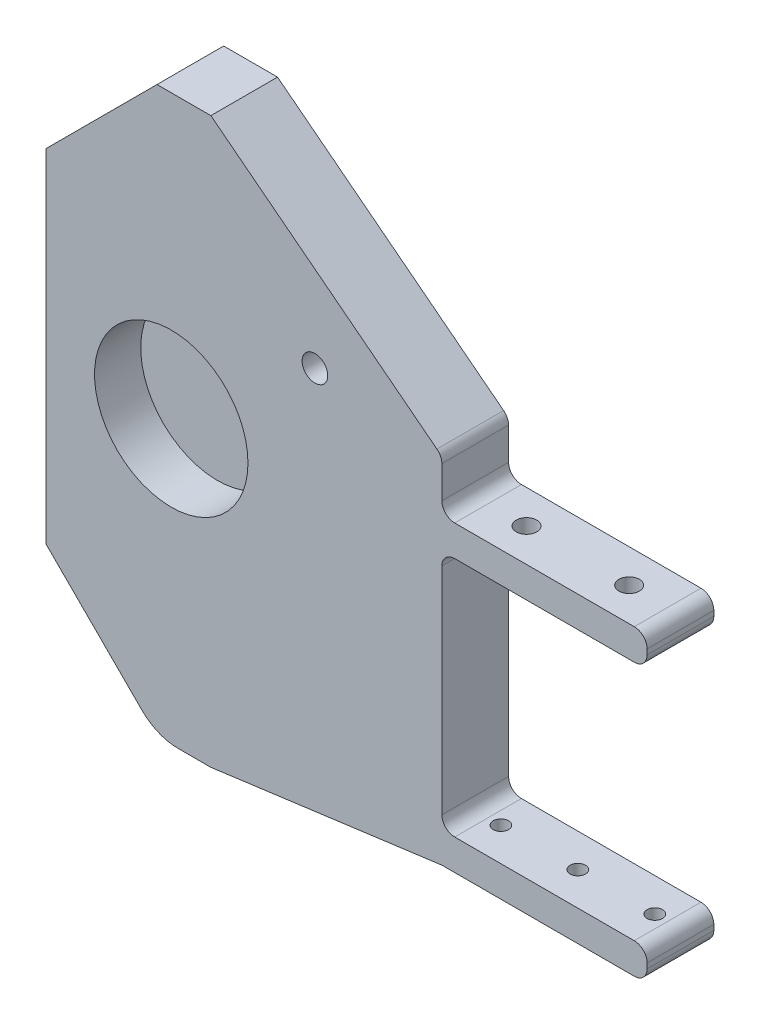
SolidWorks part; units mm, degrees
material "5052-H36"
ref_plane "Plano frontal" through (0, 0, 0) normal (0, 0, 1) x (1, 0, 0)
ref_plane "Plano superior" through (0, 0, 0) normal (0, 1, 0) x (1, 0, 0)
ref_plane "Plano direito" through (0, 0, 0) normal (1, 0, 0) x (0, 0, -1)
sketch "Esboço1" plane through (0, 0, 0) normal (0, 0, 1) x (1, 0, 0)
  line L0 (79.1281, 0) -> (0, 0) construction
  line L3 (4.9801, 55) -> (32.742, 55)
  line L6 (32.742, 55) -> (-22.7817, 55)
  line L12 (-22.7817, 55) -> (-44.3754, 33.4063)
  line L14 (-44.3754, -33.4063) -> (-22.7817, -55)
  line L15 (-22.7817, -55) -> (32.742, -55)
  line L18 (393.8557, 316.0739) -> (396.402, 318.6203) [skipped]
  line L19 (55, 501.996) -> (55, 520.8093) [skipped]
  line L20 (-316.0739, 393.8557) -> (-318.6203, 396.402) [skipped]
  line L21 (32.742, 55) -> (32.742, 10)
  line L22 (32.742, -49) -> (32.742, -55)
  line L23 (32.742, -49) -> (72.742, -49)
  line L25 (32.742, -43) -> (72.742, -43)
  line L26 (72.742, -49) -> (72.742, -43)
  line L27 (32.742, 4) -> (32.742, -43)
  line L28 (32.742, 4) -> (72.742, 4)
  line L30 (32.742, 10) -> (72.742, 10)
  line L31 (72.742, 4) -> (72.742, 10)
  line L32 (-44.3754, 33.4063) -> (-44.3754, -33.4063)
  line L34 (-55, 7.7563) -> (-55, -6.3461) [skipped]
  circle A0 centre (0, 0) radius 15 construction
  arc A3 (4.9801, 55) -> (0, -55.225) centre (0, 0) ccw construction
  point P14 (4.9801, 55)
  dimension "D1" = 30
  dimension "D5" = 110
  dimension "D6" = 40
  dimension "D7" = 6
  dimension "D8" = 6
  dimension "D9" = 45
extrude "Ressalto-extrusão1" add sketch "Esboço1" along normal mid plane 13 contours L14 L15 L3 L6 L12 A0 region at (-0.7875, -1.1016, 0)
sketch "Esboço2" plane through (0, 0, 6.5) normal (0, 0, 1) x (1, 0, 0)
  circle A1 centre (-20, 0) radius 14.95
  dimension "D1" = 29.9
  dimension "D2" = 20
extrude "Corte-extrusão1" cut sketch "Esboço2" against normal blind 9
sketch "Esboço3" plane through (0, 0, 6.5) normal (0, 0, 1) x (1, 0, 0)
  line L0 (-22.7817, -55) -> (32.742, -55) construction
  line L1 (-12.2817, -55) -> (32.742, -49)
  line L2 (32.742, -49) -> (32.742, -55)
  line L3 (32.742, -55) -> (-12.2817, -55)
  line L4 (-12.2817, -55) -> (-12.2817, 66.3095) construction
  line L6 (32.742, 10) -> (72.742, 10) construction
  line L11 (32.742, 55) -> (-12.2817, 55)
  line L12 (-12.2817, 55) -> (32.742, 20)
  line L13 (32.742, 20) -> (32.742, 55)
  circle A0 centre (8, 22.5) radius 2.5
  point P0 (-12.2817, -55)
  dimension "D2" = 5
  dimension "D1" = 10.5
  dimension "D3" = 22.5
  dimension "D4" = 28
  dimension "D5" = 10
extrude "Corte-extrusão2" cut sketch "Esboço3" against normal blind 13
fillet "Filete1" radius 10 1 edges at (-22.7817, -55, 0)
sketch "Esboço4" plane through (0, 0, -6.5) normal (0, 0, -1) x (-1, 0, 0)
  line L0 (44.3754, 33.4063) -> (44.3754, -33.4063) construction
  circle A0 centre (36.3754, 8.4063) radius 2
  circle A1 centre (12.9554, -16.5937) radius 2
  circle A2 centre (22.3754, -27.5937) radius 2
  dimension "D1" = 4
  dimension "D2" = 25
  dimension "D3" = 8
  dimension "D4" = 23.42
  dimension "D5" = 25
  dimension "D6" = 36
  dimension "D7" = 14
extrude "Corte-extrusão3" cut sketch "Esboço4" against normal blind 10
sketch "Esboço6" plane through (0, 10, 0) normal (0, 1, 0) x (1, 0, 0)
  line L0 (32.742, -6.5) -> (72.742, -6.5) construction
  circle A0 centre (42.742, -0.0016) radius 2
  circle A1 centre (62.742, -0.0016) radius 2
  circle A2 centre (42.742, -0.0016) radius 2 construction
  dimension "D1" = 20
  dimension "D2" = 6.4984
extrude "Corte-extrusão4" cut sketch "Esboço6" against normal blind 10
sketch "Esboço7" plane through (0, -49, 0) normal (0, -1, 0) x (1, 0, 0)
  line L0 (32.742, -6.5) -> (72.742, -6.5) construction
  line L1 (37.742, 0) -> (67.742, 0) construction
  line L2 (72.742, 6.5) -> (72.742, -6.5) construction
  circle A0 centre (37.742, 0) radius 1.5
  circle A1 centre (52.742, 0) radius 1.5
  circle A2 centre (67.742, 0) radius 1.5
  dimension "D1" = 3
  dimension "D2" = 6.5
  dimension "D3" = 5
  dimension "D4" = 20
  dimension "D5" = 35
extrude "Corte-extrusão5" cut sketch "Esboço7" against normal blind 10
fillet "Filete2" radius 2.5 8 edges at (72.742, -49, 0) (72.742, -43, 0) (72.742, 4, 0) (72.742, 10, 0) (32.742, 20, 0) (32.742, -43, 0) (32.742, 10, 0) (32.742, 4, 0)
